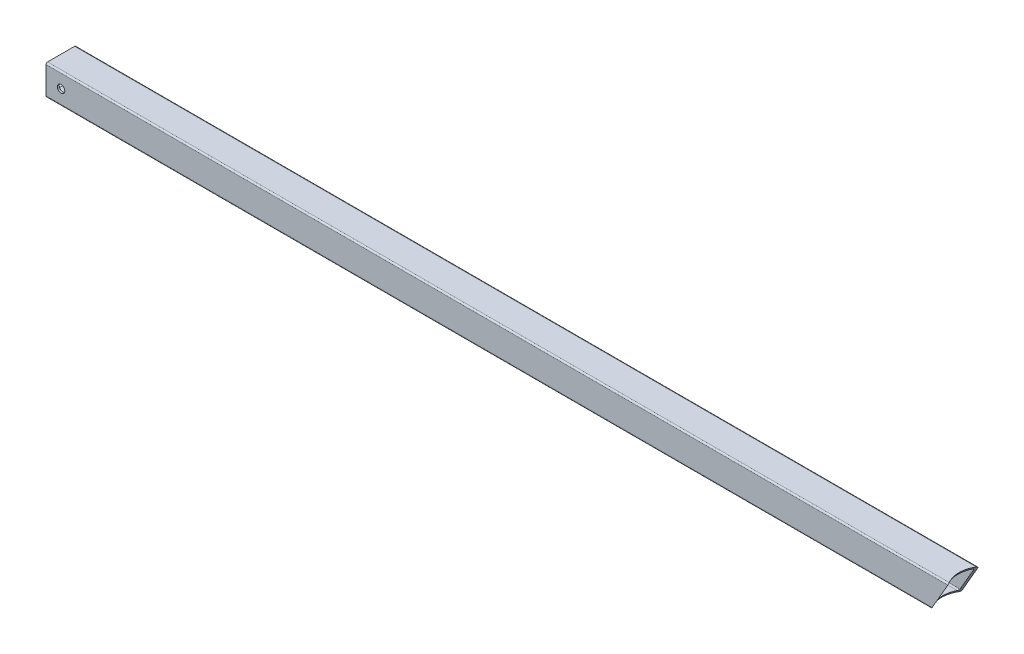
SolidWorks part; units mm, degrees
ref_plane "Front" through (0, 0, 0) normal (0, 0, 1) x (1, 0, 0)
ref_plane "Top" through (0, 0, 0) normal (0, 1, 0) x (1, 0, 0)
ref_plane "Right" through (0, 0, 0) normal (1, 0, 0) x (0, 0, -1)
sketch "Sketch1" plane through (0, 0, 0) normal (1, 0, 0) x (0, 0, -1)
  line L0 (-11.049, 0) -> (-12.7, 0) construction
  line L1 (11.43, -12.7) -> (-11.43, -12.7) construction
  line L2 (12.7, -11.43) -> (12.7, 11.43) construction
  line L3 (11.43, 12.7) -> (-11.43, 12.7) construction
  line L4 (-12.7, -11.43) -> (-12.7, 11.43) construction
  line L5 (12.7, -12.7) -> (-12.7, 12.7) construction
  line L6 (12.7, 12.7) -> (-12.7, -12.7) construction
  line L7 (9.9441, 11.049) -> (-9.9441, 11.049) construction
  line L8 (11.049, 9.9441) -> (11.049, -9.9441) construction
  line L9 (9.9441, -11.049) -> (-9.9441, -11.049) construction
  line L10 (-11.049, 9.9441) -> (-11.049, -9.9441) construction
  line L11 (11.049, 11.049) -> (-11.049, -11.049) construction
  line L12 (11.049, -11.049) -> (-11.049, 11.049) construction
  line L13 (0, -11.049) -> (0, -12.7) construction
  line L14 (11.049, -9.9441) -> (11.049, -12.7) construction
  line L15 (11.049, 0) -> (12.7, 0) construction
  line L16 (11.049, -12.7) -> (12.7, -12.7) construction
  arc A0 (-9.9441, -11.049) -> (-11.049, -9.9441) centre (-9.9441, -9.9441) cw construction
  arc A1 (11.049, -9.9441) -> (9.9441, -11.049) centre (9.9441, -9.9441) cw construction
  arc A2 (9.9441, 11.049) -> (11.049, 9.9441) centre (9.9441, 9.9441) cw construction
  arc A3 (-9.9441, 11.049) -> (-11.049, 9.9441) centre (-9.9441, 9.9441) ccw construction
  arc A4 (11.43, -12.7) -> (12.7, -11.43) centre (11.43, -11.43) ccw construction
  arc A5 (12.7, 11.43) -> (11.43, 12.7) centre (11.43, 11.43) ccw construction
  arc A6 (-11.43, 12.7) -> (-12.7, 11.43) centre (-11.43, 11.43) ccw construction
  arc A7 (-11.43, -12.7) -> (-12.7, -11.43) centre (-11.43, -11.43) cw construction
  point P0 (0, 0)
  point P6 (0, 0)
  dimension "D2" = 1.1049
  dimension "D3" = 1.27
  dimension "Outside Width" = 25.4
  dimension "Ouside Height" = 25.4
  dimension "Inside Height" = 22.098
  dimension "Wall Thickness" = 1.651
sketch "Sketch2" plane through (0, 0, 0) normal (0, 0, 1) x (1, 0, 0)
  line L0 (-381, 0) -> (381, 0) construction
  point P3 (-357.251, 0)
  point P4 (357.251, 0)
  dimension "Length" = 762
  dimension "D1" = 23.749
  dimension "D2" = 23.749
sketch "Sketch4" plane through (0, 0, 0) normal (1, 0, 0) x (0, 0, -1)
  line L8 (12.7, -11.43) -> (12.7, 11.43)
  line L9 (11.43, 12.7) -> (-11.43, 12.7)
  line L10 (-12.7, -11.43) -> (-12.7, 11.43)
  line L11 (11.43, -12.7) -> (-11.43, -12.7)
  line L12 (11.049, 9.9441) -> (11.049, -9.9441)
  line L13 (9.9441, -11.049) -> (-9.9441, -11.049)
  line L14 (-11.049, 9.9441) -> (-11.049, -9.9441)
  line L15 (9.9441, 11.049) -> (-9.9441, 11.049)
  arc A8 (12.7, 11.43) -> (11.43, 12.7) centre (11.43, 11.43) ccw
  arc A9 (-11.43, 12.7) -> (-12.7, 11.43) centre (-11.43, 11.43) ccw
  arc A10 (-12.7, -11.43) -> (-11.43, -12.7) centre (-11.43, -11.43) ccw
  arc A11 (11.43, -12.7) -> (12.7, -11.43) centre (11.43, -11.43) ccw
  arc A12 (9.9441, -11.049) -> (11.049, -9.9441) centre (9.9441, -9.9441) ccw
  arc A13 (-11.049, -9.9441) -> (-9.9441, -11.049) centre (-9.9441, -9.9441) ccw
  arc A14 (-9.9441, 11.049) -> (-11.049, 9.9441) centre (-9.9441, 9.9441) ccw
  arc A15 (11.049, 9.9441) -> (9.9441, 11.049) centre (9.9441, 9.9441) ccw
extrude "Boss-Extrude1" add sketch "Sketch4" along normal up to vertex (-381 mm away) and the other way up to vertex (-381 mm away) up to point (-381, 0, 0) other way up to point (381, 0, 0)
sketch "Sketch5" plane through (0, 0, 12.7) normal (0, 0, 1) x (1, 0, 0)
  line L0 (381, 12.7) -> (-381, 12.7) construction
  line L1 (-381, 11.43) -> (-381, -11.43) construction
  circle A0 centre (-368.3, 0) radius 3.175
  dimension "D1" = 12.7
  dimension "D2" = 12.7
  dimension "D3" = 6.35
extrude "Cut-Extrude1" cut sketch "Sketch5" against normal through all
ref_plane "Plane1" through (100.7493, 174.5028, 0) normal (0.5, 0.866, 0) x (0, 0, 1)
sketch "Sketch6" plane through (100.7493, 174.5028, 0) normal (0.5, 0.866, 0) x (0, 0, 1)
  line L1 (-12.7, 324.2407) -> (-12.7, -335.6707) construction
  circle A0 centre (0, 345.998) radius 25.4
  ellipse E0 centre (11.43, 324.2407) end of major axis (12.7, 324.2407) minor radius 0.635 (11.43, 323.6057) -> (12.7, 324.2407) ccw construction
  point P2 (0, 0)
  point P3 (0, 0)
  point P6 (0, 0)
  point P7 (0, 0)
  point P8 (0, 410.0342)
  dimension "D1" = 50.8
  dimension "D2" = 12.7
extrude "Cut-Extrude2" cut sketch "Sketch6" against normal through all
equation "\"D3@Sketch1\"=\"Outside Width@Sketch1\"*.05"
equation "\"D2@Sketch1\" = \"Inside Height@Sketch1\" * .05"
equation "\"D1@Sketch2\"=\"Outside Width@Sketch1\"-\"Wall Thickness@Sketch1\""
equation "\"D2@Sketch2\"=\"D1@Sketch2\""
